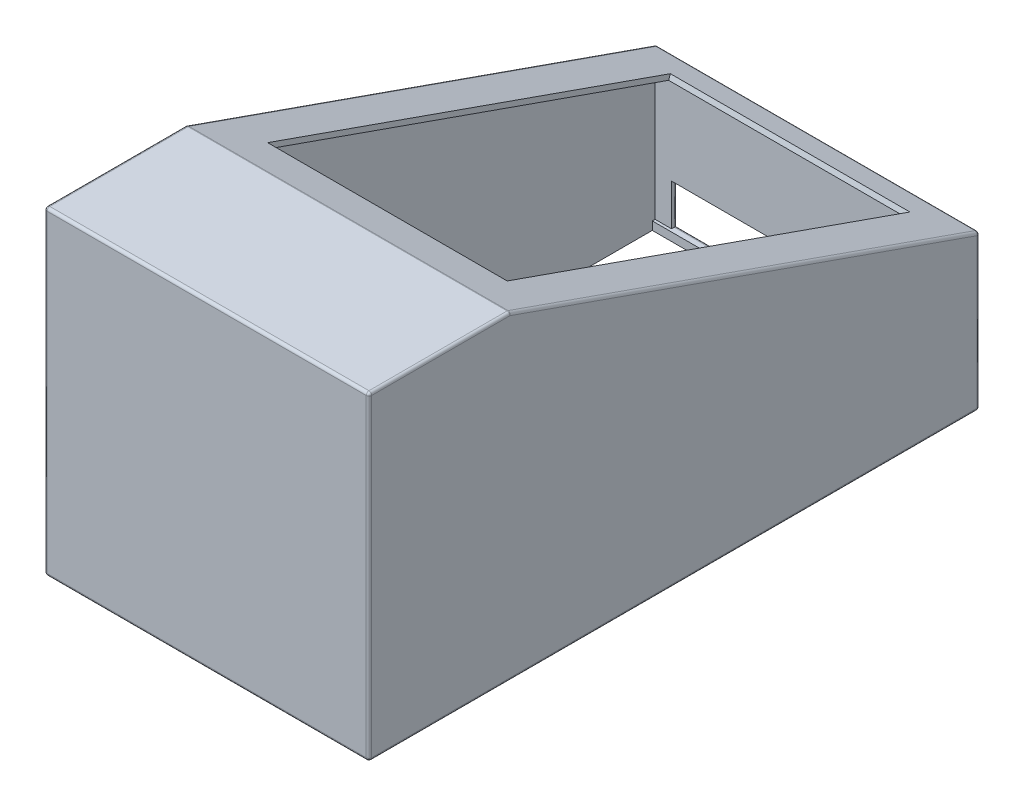
SolidWorks part; units mm, degrees
ref_plane "Alzado" through (0, 0, 0) normal (0, 0, 1) x (1, 0, 0)
ref_plane "Planta" through (0, 0, 0) normal (0, 1, 0) x (1, 0, 0)
ref_plane "Vista lateral" through (0, 0, 0) normal (1, 0, 0) x (0, 0, -1)
sketch "Sketch1" plane through (0, 0, 0) normal (1, 0, 0) x (0, 0, -1)
  line L3 (157.3381, -22.7425) -> (157.3381, 37.2575) construction
  line L4 (157.3381, 37.2575) -> (50.3381, 74.8888)
  line L7 (50.3381, 74.8888) -> (-13.2647, 97.2575)
  line L8 (-13.2647, 97.2575) -> (-64.6619, 97.2575)
  line L9 (-64.6619, 97.2575) -> (-64.6619, 95.2575)
  line L10 (-64.6619, 95.2575) -> (-13.2647, 95.2575)
  line L11 (-13.2647, 95.2575) -> (157.3381, 35.2575)
  line L12 (157.3381, 35.2575) -> (157.3381, -22.7425)
  line L13 (157.3381, -22.7425) -> (159.3381, -22.7425)
  line L14 (157.3381, 37.2575) -> (159.3381, 36.5258)
  line L15 (159.3381, 36.5258) -> (159.3381, -22.7425)
extrude "Boss-Extrude1" add sketch "Sketch1" along normal blind 118
sketch "Sketch2" plane through (0, 0, -159.3381) normal (0, 0, -1) x (-1, 0, 0)
  line L0 (0, -22.7425) -> (-8, -22.7425) construction
  line L1 (-118, -22.7425) -> (0, -22.7425) construction
  line L3 (-8, -22.7425) -> (-52, -22.7425)
  line L4 (-8, -22.7425) -> (-8, -0.7425)
  line L5 (-8, -0.7425) -> (-52, -0.7425)
  line L6 (-52, -22.7425) -> (-52, -0.7425)
  dimension "D1" = 8
  dimension "D2" = 22
  dimension "D3" = 44
extrude "Cut-Extrude1" cut sketch "Sketch2" against normal blind 118
sketch "Sketch3" plane through (0, 95.2575, 0) normal (0, -1, 0) x (1, 0, 0)
  line L0 (118, 64.6619) -> (118, 13.2647) construction
  line L1 (0, 64.6619) -> (118, 64.6619)
  line L2 (0, 64.6619) -> (0, 62.6619)
  line L3 (0, 62.6619) -> (118, 62.6619)
  line L4 (118, 64.6619) -> (118, 62.6619)
  dimension "D1" = 2
extrude "Boss-Extrude2" add sketch "Sketch3" along normal blind 114.04
sketch "Sketch5" plane through (0, 0, 64.6619) normal (0, 0, 1) x (1, 0, 0)
  line L7 (118, -18.7825) -> (0, -18.7825) construction
  line L8 (108, -18.7825) -> (69, -18.7825)
  line L9 (108, -18.7825) -> (108, -8.7825)
  line L10 (108, -8.7825) -> (69, -8.7825)
  line L11 (69, -18.7825) -> (69, -8.7825)
  line L12 (59, -18.7825) -> (59, -8.6532) construction
  line L13 (118, 97.2575) -> (118, -18.7825) construction
  dimension "D1" = 10
  dimension "D2" = 10
  dimension "D3" = 10
extrude "Boss-Extrude3" add sketch "Sketch5" against normal blind 10
sketch "Sketch6" plane through (0, 0, 62.6619) normal (0, 0, -1) x (-1, 0, 0)
  line L0 (0, -18.7825) -> (0, 95.2575) construction
  line L1 (-118, -18.7825) -> (0, -18.7825)
  line L2 (-118, -18.7825) -> (-118, -16.7825)
  line L3 (-118, -16.7825) -> (0, -16.7825)
  line L4 (0, -18.7825) -> (0, -16.7825)
  dimension "D1" = 2
extrude "Boss-Extrude4" add sketch "Sketch6" along normal blind 1
sketch "Sketch7" plane through (0, 0, 64.6619) normal (0, 0, 1) x (1, 0, 0)
  line L1 (0, -18.7825) -> (118, -18.7825)
  line L2 (0, -18.7825) -> (0, -22.7425)
  line L3 (0, -22.7425) -> (118, -22.7425)
  line L4 (118, -18.7825) -> (118, -22.7425)
extrude "Cut-Extrude2" cut sketch "Sketch7" against normal through all
sketch "Sketch8" plane through (0, 0, -159.3381) normal (0, 0, -1) x (-1, 0, 0)
  line L0 (0, -18.7825) -> (0, 36.5258) construction
  line L1 (-118, -18.7825) -> (0, -18.7825)
  line L2 (-118, -18.7825) -> (-118, -15.7825)
  line L3 (-118, -15.7825) -> (0, -15.7825)
  line L4 (0, -18.7825) -> (0, -15.7825)
  dimension "D1" = 3
extrude "Boss-Extrude5" add sketch "Sketch8" against normal up to vertex (2 mm away) up to point (0, -18.7825, -157.3381)
sketch "Sketch9" plane through (0, 0, 0) normal (-1, 0, 0) x (0, 0, 1)
  line L0 (13.2647, 95.2575) -> (-157.3381, 35.2575) construction
  line L1 (-157.3381, -18.7825) -> (-155.3381, -18.7825)
  line L2 (-157.3381, -18.7825) -> (-157.3381, 35.9609)
  line L3 (-157.3381, 35.9609) -> (-155.3381, 35.9609)
  line L4 (-155.3381, -18.7825) -> (-155.3381, 35.9609)
  dimension "D1" = 2
extrude "Boss-Extrude6" add sketch "Sketch9" against normal up to vertex (118 mm away) up to point (118, 35.2575, -157.3381)
sketch "Sketch12" plane through (0, 0, -157.3381) normal (0, 0, -1) x (-1, 0, 0)
  line L1 (-52, -15.7825) -> (-8, -15.7825)
  line L2 (-52, -15.7825) -> (-52, -0.7425)
  line L3 (-52, -0.7425) -> (-8, -0.7425)
  line L4 (-8, -15.7825) -> (-8, -0.7425)
extrude "Cut-Extrude4" cut sketch "Sketch12" against normal blind 116
sketch "Sketch13" plane through (0, 0, 0) normal (-1, 0, 0) x (0, 0, 1)
  line L1 (-159.3381, -18.7825) -> (-157.3381, -18.7825)
  line L2 (-159.3381, -18.7825) -> (-159.3381, 42.3145)
  line L3 (-159.3381, 42.3145) -> (-157.3381, 42.3145)
  line L4 (-157.3381, -18.7825) -> (-157.3381, 42.3145)
  dimension "D1" = 2
extrude "Cut-Extrude5" cut sketch "Sketch13" against normal through all
sketch "Sketch15" plane through (0, 0, -155.3381) normal (0, 0, 1) x (1, 0, 0)
  line L0 (118, -18.7825) -> (118, 35.9609) construction
  line L1 (0, -18.7825) -> (118, -18.7825)
  line L2 (0, -18.7825) -> (0, -15.7825)
  line L3 (0, -15.7825) -> (118, -15.7825)
  line L4 (118, -18.7825) -> (118, -15.7825)
  dimension "D1" = 3
extrude "Boss-Extrude7" add sketch "Sketch15" along normal blind 1
sketch "Sketch26" plane through (118, 0, 0) normal (1, 0, 0) x (0, 0, -1)
  line L0 (-64.6619, -18.7825) -> (-64.6619, 97.2575)
  line L1 (-64.6619, 97.2575) -> (-13.2647, 97.2575)
  line L2 (-13.2647, 97.2575) -> (157.3381, 37.2575)
  line L3 (157.3381, 37.2575) -> (157.3381, -18.7825)
  line L4 (157.3381, -18.7825) -> (-64.6619, -18.7825)
extrude "Boss-Extrude13" add sketch "Sketch26" against normal blind 2
sketch "Sketch28" plane through (0, 0, 0) normal (-1, 0, 0) x (0, 0, 1)
  line L0 (64.6619, -18.7825) -> (64.6619, 97.2575)
  line L1 (64.6619, 97.2575) -> (13.2647, 97.2575)
  line L2 (13.2647, 97.2575) -> (-157.3381, 37.2575)
  line L3 (-157.3381, 37.2575) -> (-157.3381, -18.7825)
  line L4 (-157.3381, -18.7825) -> (64.6619, -18.7825)
extrude "Boss-Extrude16" add sketch "Sketch28" against normal blind 2
fillet "Fillet9" radius 1 20 edges at (30, -0.7425, -157.3381) (52, -8.2625, -157.3381) (30, -15.7825, -157.3381) (8, -8.2625, -157.3381) (59, -18.7825, -157.3381) (118, 9.2375, -157.3381) (118, -18.7825, -46.3381) (118, 39.2375, 64.6619) (59, -18.7825, 64.6619) (118, 97.2575, 38.9633) (59, 97.2575, 64.6619) (59, 37.2575, -157.3381) (118, 67.2575, -72.0367) (59, 97.2575, 13.2647) (0, 67.2575, -72.0367) (0, 97.2575, 38.9633) (0, 39.2375, 64.6619) (0, -18.7825, -46.3381) (0, 9.2375, -157.3381) (52, -0.7425, -156.3381)
fillet "Fillet10" radius 1 9 edges at (59, 95.2575, 13.2647) (116, 65.6092, -71.0367) (59, 35.9609, -155.3381) (2, 65.6092, -71.0367) (116, 95.2575, 37.9633) (116, 39.2375, 62.6619) (2, 39.2375, 62.6619) (59, 95.2575, 62.6619) (2, 95.2575, 37.9633)
sketch "Sketch30" plane through (0, 82.4004, -28.9797) normal (0, 0.9434, -0.3318) x (1, 0, 0)
  line L1 (15.45, 125.5898) -> (102.55, 125.5898)
  line L2 (15.45, 125.5898) -> (15.45, -29.6102)
  line L3 (15.45, -29.6102) -> (102.55, -29.6102)
  line L4 (102.55, 125.5898) -> (102.55, -29.6102)
  line L7 (1, 135.3569) -> (1, -44.6102) construction
  line L9 (1, -44.6102) -> (117, -44.6102) construction
  dimension "D1" = 87.1
  dimension "D2" = 155.2
  dimension "D3" = 14.45
  dimension "D4" = 15
extrude "Cut-Extrude7" cut sketch "Sketch30" against normal through all
